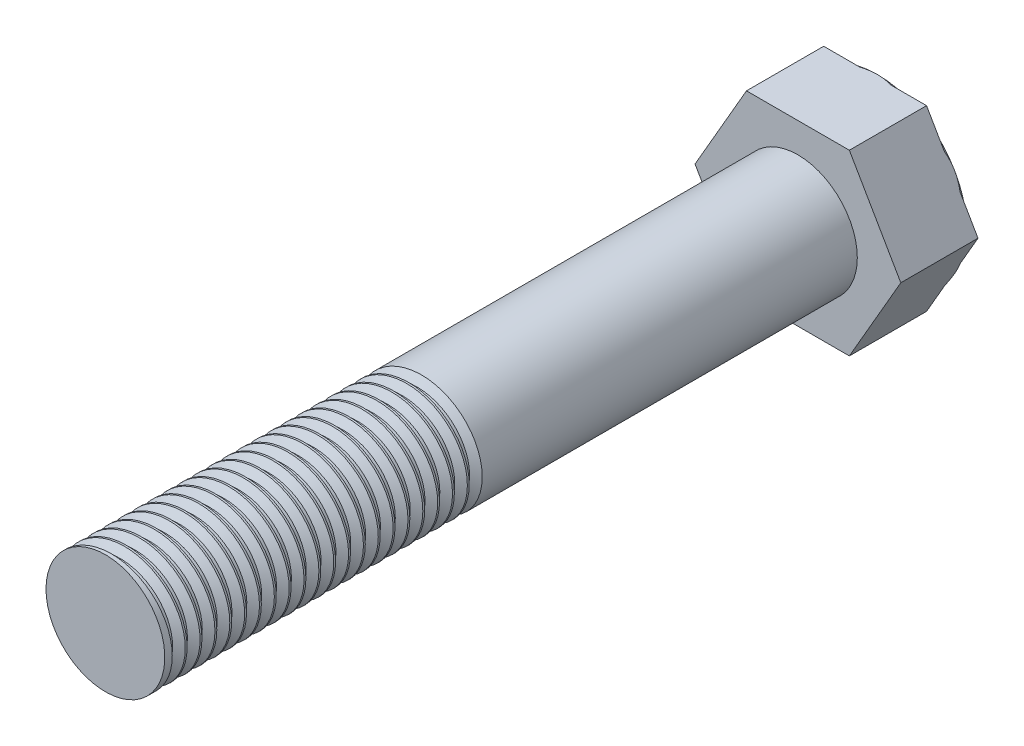
SolidWorks part; units mm, degrees
ref_plane "Front Plane" through (0, 0, 0) normal (0, 0, 1) x (1, 0, 0)
ref_plane "Top Plane" through (0, 0, 0) normal (0, 1, 0) x (1, 0, 0)
ref_plane "Right Plane" through (0, 0, 0) normal (1, 0, 0) x (0, 0, -1)
sketch "Sketch1" plane through (0, 0, 0) normal (0, 0, 1) x (1, 0, 0)
  circle A0 centre (0, 0) radius 10
  dimension "D1" = 20
extrude "Boss-Extrude1" add sketch "Sketch1" along normal blind 116.6
sketch "Sketch2" plane through (0, 0, 0) normal (0, 0, -1) x (-1, 0, 0)
  line L1 (17.3205, 0) -> (8.6603, 15)
  line L2 (8.6603, 15) -> (-8.6603, 15)
  line L3 (-8.6603, 15) -> (-17.3205, 0)
  line L4 (-17.3205, 0) -> (-8.6603, -15)
  line L5 (-8.6603, -15) -> (8.6603, -15)
  line L6 (8.6603, -15) -> (17.3205, 0)
  circle A0 centre (0, 0) radius 15 construction
  dimension "D1" = 30
extrude "Boss-Extrude2" add sketch "Sketch2" along normal blind 13.4
sketch "Sketch3" plane through (0, 0, -13.4) normal (0, 0, -1) x (-1, 0, 0)
  circle A0 centre (0, 0) radius 15
  dimension "D1" = 30
extrude "Cut-Extrude1" cut sketch "Sketch3" against normal blind 0.4 draft 30 flip side to cut
thread "Thread1" pitch 2.5 method cut profile "Thread Profile1" start angle 0, offset 0, length 52, pitch 2.5, diameter 20
ref_plane "Plane1" through (-10, 0, 116.6) normal (0, -1, 0) x (-1, 0, 0)
sketch "Thread Profile1" plane through (-10, 0, 116.6) normal (0, -1, 0) x (-1, 0, 0)
  line L0 (0, 0) -> (0, 2.5) construction
  line L11 (0, 0) -> (0, 2.1875)
  line L12 (0, 2.1875) -> (-1.3532, 1.4062)
  line L13 (-1.3532, 1.4062) -> (-1.3532, 0.7812)
  line L15 (-1.3532, 0.7812) -> (0, 0)
  line L17 (-1.3532, 1.0937) -> (0, 1.0937) construction
  point P2 (0, 0)
  dimension "Pitch" = 2.5
  dimension "Profile_Angle" = 60
  dimension "Profile_Land" = 0.625
  dimension "Profile_Height" = 1.3532
equation "\"D1@Boss-Extrude1\"=130-13.4"
